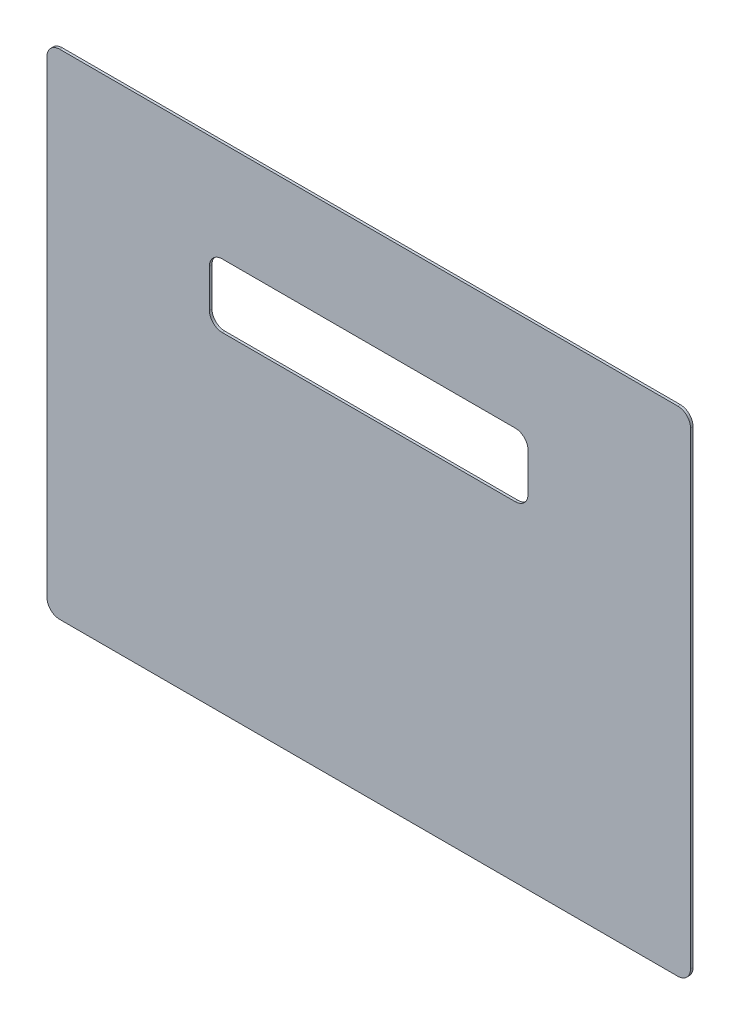
SolidWorks part; units mm, degrees
material "Acrylic (Medium-high impact)"
ref_plane "Front Plane" through (0, 0, 0) normal (0, 0, 1) x (1, 0, 0)
ref_plane "Top Plane" through (0, 0, 0) normal (0, 1, 0) x (1, 0, 0)
ref_plane "Right Plane" through (0, 0, 0) normal (1, 0, 0) x (0, 0, -1)
sketch "Sketch1" plane through (0, 0, 0) normal (0, 0, 1) x (1, 0, 0)
  line L1 (-500, -382.5) -> (500, -382.5) construction
  line L2 (-500, -382.5) -> (-500, 382.5) construction
  line L3 (-500, 382.5) -> (500, 382.5) construction
  line L4 (500, -382.5) -> (500, 382.5) construction
  line L5 (-500, -382.5) -> (500, 382.5) construction
  line L6 (-500, 382.5) -> (500, -382.5) construction
  line L7 (-505, -387.5) -> (505, -387.5)
  line L8 (-505, -387.5) -> (-505, 387.5)
  line L9 (-505, 387.5) -> (505, 387.5)
  line L10 (505, -387.5) -> (505, 387.5)
  line L11 (-505, -387.5) -> (505, 387.5) construction
  line L12 (-505, 387.5) -> (505, -387.5) construction
  point P0 (0, 0)
  dimension "D1" = 1000
  dimension "D2" = 765
  dimension "D3" = 5
  dimension "D4" = 5
extrude "Boss-Extrude1" add sketch "Sketch1" along normal blind 4
fillet "Fillet1" radius 20 4 edges at (-505, -387.5, 2) (-505, 387.5, 2) (505, 387.5, 2) (505, -387.5, 2)
sketch "Sketch2" plane through (0, 0, 4) normal (0, 0, 1) x (1, 0, 0)
  line L0 (0, 0) -> (0, 230) construction
  line L1 (250, 130) -> (-250, 130)
  line L2 (250, 130) -> (250, 230)
  line L3 (250, 230) -> (-250, 230)
  line L4 (-250, 130) -> (-250, 230)
  point P6 (0, 0)
  point P7 (0, 0)
  dimension "D1" = 500
  dimension "D2" = 100
  dimension "D3" = 230
extrude "Cut-Extrude1" cut sketch "Sketch2" against normal blind 10
fillet "Fillet2" radius 20 4 edges at (-250, 130, 2) (-250, 230, 2) (250, 130, 2) (250, 230, 2)
